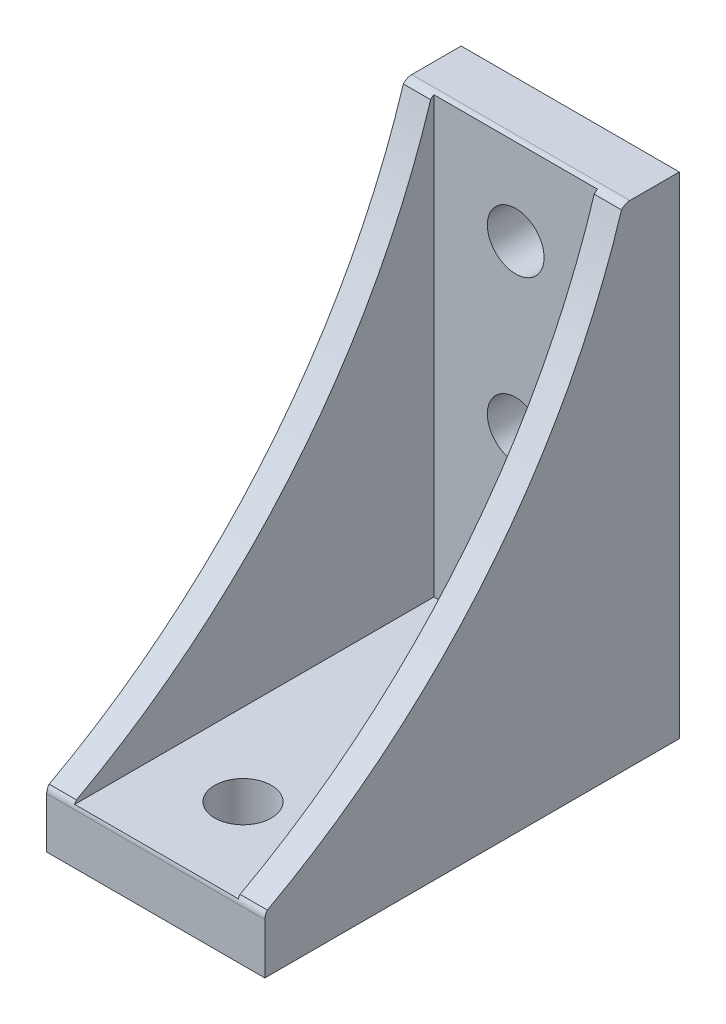
SolidWorks part; units mm, degrees
ref_plane "Front Plane" through (0, 0, 0) normal (0, 0, 1) x (1, 0, 0)
ref_plane "Top Plane" through (0, 0, 0) normal (0, 1, 0) x (1, 0, 0)
ref_plane "Right Plane" through (0, 0, 0) normal (1, 0, 0) x (0, 0, -1)
ref_plane "Plane1" through (0, 0, 0) normal (1, 0, 0) x (0, 0, -1)
sketch "Sketch1" plane through (0, 0, 0) normal (1, 0, 0) x (0, 0, -1)
  line L0 (-38, 0) -> (0, 0)
  line L1 (0, 0) -> (0, 45)
  line L2 (0, 45) -> (-4.5286, 45)
  line L3 (-5.3, 44.6364) -> (-37.7714, 5.2771)
  line L4 (-38, 4.6407) -> (-38, 0)
  arc A0 (-4.5286, 45) -> (-5.3, 44.6364) centre (-4.5286, 44) ccw
  arc A1 (-37.7714, 5.2771) -> (-38, 4.6407) centre (-37, 4.6407) ccw
extrude "Boss-Extrude1" add sketch "Sketch1" against normal blind 10 and the other way blind 10
ref_plane "Plane2" through (0, 0, 0) normal (1, 0, 0) x (0, 0, -1)
sketch "Sketch2" plane through (0, 0, 0) normal (1, 0, 0) x (0, 0, -1)
  line L0 (-43, 5) -> (-5, 5)
  line L1 (-5, 5) -> (-5, 50)
  line L2 (-5, 50) -> (-43, 50)
  line L3 (-43, 50) -> (-43, 5)
extrude "Cut-Extrude1" cut sketch "Sketch2" against normal blind 7.5 and the other way blind 7.5
ref_plane "Plane3" through (0, 0, 0) normal (1, 0, 0) x (0, 0, -1)
sketch "Sketch3" plane through (0, 0, 0) normal (1, 0, 0) x (0, 0, -1)
  line L0 (-5.3, 44.6364) -> (-37.7714, 5.2771)
  arc A0 (-37.7714, 5.2771) -> (-5.3, 44.6364) centre (-69.8148, 64.787) ccw
extrude "Cut-Extrude2" cut sketch "Sketch3" against normal blind 10 and the other way blind 10
ref_plane "Plane4" through (0, 0, 0) normal (0, 1, 0) x (1, 0, 0)
sketch "Sketch4" plane through (0, 0, 0) normal (0, 1, 0) x (1, 0, 0)
  circle A0 centre (0, -10) radius 2.6
extrude "Cut-Extrude3" cut sketch "Sketch4" along normal blind 5
ref_plane "Plane5" through (0, 0, 0) normal (0, 1, 0) x (1, 0, 0)
sketch "Sketch5" plane through (0, 0, 0) normal (0, 1, 0) x (1, 0, 0)
  circle A0 centre (0, -30) radius 2.6
extrude "Cut-Extrude4" cut sketch "Sketch5" along normal blind 5
ref_plane "Plane6" through (0, 0, 0) normal (0, 0, 1) x (1, 0, 0)
sketch "Sketch6" plane through (0, 0, 0) normal (0, 0, 1) x (1, 0, 0)
  circle A0 centre (0, 22) radius 2.6
extrude "Cut-Extrude5" cut sketch "Sketch6" along normal blind 5
ref_plane "Plane7" through (0, 0, 0) normal (0, 0, 1) x (1, 0, 0)
sketch "Sketch7" plane through (0, 0, 0) normal (0, 0, 1) x (1, 0, 0)
  circle A0 centre (0, 37) radius 2.6
extrude "Cut-Extrude6" cut sketch "Sketch7" along normal blind 5
ref_plane "Plane8" through (0, 0, 0) normal (0, 1, 0) x (1, 0, 0)
sketch "Sketch8" plane through (0, 0, 0) normal (0, 1, 0) x (1, 0, 0)
  line L0 (-10, 0) -> (-10, -38)
  line L1 (-10, -38) -> (10, -38)
  line L2 (10, -38) -> (10, 0)
  line L3 (10, 0) -> (-10, 0)
extrude "Boss-Extrude2" add sketch "Sketch8" against normal blind 0.8
ref_plane "Plane9" through (0, 0, 0) normal (0, 0, 1) x (1, 0, 0)
sketch "Sketch9" plane through (0, 0, 0) normal (0, 0, 1) x (1, 0, 0)
  line L0 (-10, 0) -> (10, 0)
  line L1 (10, 0) -> (10, 45)
  line L2 (10, 45) -> (-10, 45)
  line L3 (-10, 45) -> (-10, 0)
extrude "Boss-Extrude3" add sketch "Sketch9" against normal blind 0.8
ref_plane "Plane10" through (0, 0, 0) normal (0, 1, 0) x (1, 0, 0)
sketch "Sketch10" plane through (0, 0, 0) normal (0, 1, 0) x (1, 0, 0)
  line L0 (-10, 0) -> (-10, -38)
  line L1 (-10, -38) -> (10, -38)
  line L2 (10, -38) -> (10, 0)
  line L3 (10, 0) -> (-10, 0)
  line L4 (0.5, -33) -> (2, -33)
  line L5 (3, -32) -> (3, -30.5)
  line L6 (3, -30.5) -> (2.5515, -30.5)
  line L7 (0.5, -32.5515) -> (0.5, -33)
  line L8 (0.5, -27) -> (0.5, -27.4485)
  line L9 (2.5515, -29.5) -> (3, -29.5)
  line L10 (3, -29.5) -> (3, -28)
  line L11 (2, -27) -> (0.5, -27)
  line L12 (0.5, -13) -> (2, -13)
  line L13 (3, -12) -> (3, -10.5)
  line L14 (3, -10.5) -> (2.5515, -10.5)
  line L15 (0.5, -12.5515) -> (0.5, -13)
  line L16 (0.5, -7) -> (0.5, -7.4485)
  line L17 (2.5515, -9.5) -> (3, -9.5)
  line L18 (3, -9.5) -> (3, -8)
  line L19 (2, -7) -> (0.5, -7)
  line L20 (-2, -33) -> (-0.5, -33)
  line L21 (-0.5, -33) -> (-0.5, -32.5515)
  line L22 (-2.5515, -30.5) -> (-3, -30.5)
  line L23 (-3, -30.5) -> (-3, -32)
  line L24 (-3, -29.5) -> (-2.5515, -29.5)
  line L25 (-0.5, -27.4485) -> (-0.5, -27)
  line L26 (-0.5, -27) -> (-2, -27)
  line L27 (-3, -28) -> (-3, -29.5)
  line L28 (-2, -13) -> (-0.5, -13)
  line L29 (-0.5, -13) -> (-0.5, -12.5515)
  line L30 (-2.5515, -10.5) -> (-3, -10.5)
  line L31 (-3, -10.5) -> (-3, -12)
  line L32 (-3, -9.5) -> (-2.5515, -9.5)
  line L33 (-0.5, -7.4485) -> (-0.5, -7)
  line L34 (-0.5, -7) -> (-2, -7)
  line L35 (-3, -8) -> (-3, -9.5)
  arc A0 (2, -33) -> (3, -32) centre (2, -32) ccw
  arc A1 (2.5515, -30.5) -> (0.5, -32.5515) centre (0, -30) cw
  arc A2 (0.5, -27.4485) -> (2.5515, -29.5) centre (0, -30) cw
  arc A3 (3, -28) -> (2, -27) centre (2, -28) ccw
  arc A4 (2, -13) -> (3, -12) centre (2, -12) ccw
  arc A5 (2.5515, -10.5) -> (0.5, -12.5515) centre (0, -10) cw
  arc A6 (0.5, -7.4485) -> (2.5515, -9.5) centre (0, -10) cw
  arc A7 (3, -8) -> (2, -7) centre (2, -8) ccw
  arc A8 (-3, -32) -> (-2, -33) centre (-2, -32) ccw
  arc A9 (-0.5, -32.5515) -> (-2.5515, -30.5) centre (0, -30) cw
  arc A10 (-2.5515, -29.5) -> (-0.5, -27.4485) centre (0, -30) cw
  arc A11 (-2, -27) -> (-3, -28) centre (-2, -28) ccw
  arc A12 (-3, -12) -> (-2, -13) centre (-2, -12) ccw
  arc A13 (-0.5, -12.5515) -> (-2.5515, -10.5) centre (0, -10) cw
  arc A14 (-2.5515, -9.5) -> (-0.5, -7.4485) centre (0, -10) cw
  arc A15 (-2, -7) -> (-3, -8) centre (-2, -8) ccw
extrude "Cut-Extrude7" cut sketch "Sketch10" against normal blind 0.8
ref_plane "Plane11" through (0, 0, 0) normal (0, 0, 1) x (1, 0, 0)
sketch "Sketch11" plane through (0, 0, 0) normal (0, 0, 1) x (1, 0, 0)
  line L0 (-10, 45) -> (-10, 0)
  line L1 (-10, 0) -> (10, 0)
  line L2 (10, 0) -> (10, 45)
  line L3 (10, 45) -> (-10, 45)
  line L4 (-2.7, 27) -> (2.7, 27)
  line L5 (3, 27.3) -> (3, 32.7)
  line L6 (2.7, 33) -> (-2.7, 33)
  line L7 (-3, 32.7) -> (-3, 27.3)
  line L8 (-2.7, 3) -> (2.7, 3)
  line L9 (3, 3.3) -> (3, 7.7)
  line L10 (2.7, 8) -> (-2.7, 8)
  line L11 (-3, 7.7) -> (-3, 3.3)
  arc A0 (-3, 27.3) -> (-2.7, 27) centre (-2.7, 27.3) ccw
  arc A1 (2.7, 27) -> (3, 27.3) centre (2.7, 27.3) ccw
  arc A2 (3, 32.7) -> (2.7, 33) centre (2.7, 32.7) ccw
  arc A3 (-2.7, 33) -> (-3, 32.7) centre (-2.7, 32.7) ccw
  arc A4 (-3, 3.3) -> (-2.7, 3) centre (-2.7, 3.3) ccw
  arc A5 (2.7, 3) -> (3, 3.3) centre (2.7, 3.3) ccw
  arc A6 (3, 7.7) -> (2.7, 8) centre (2.7, 7.7) ccw
  arc A7 (-2.7, 8) -> (-3, 7.7) centre (-2.7, 7.7) ccw
extrude "Cut-Extrude8" cut sketch "Sketch11" against normal blind 1.25
